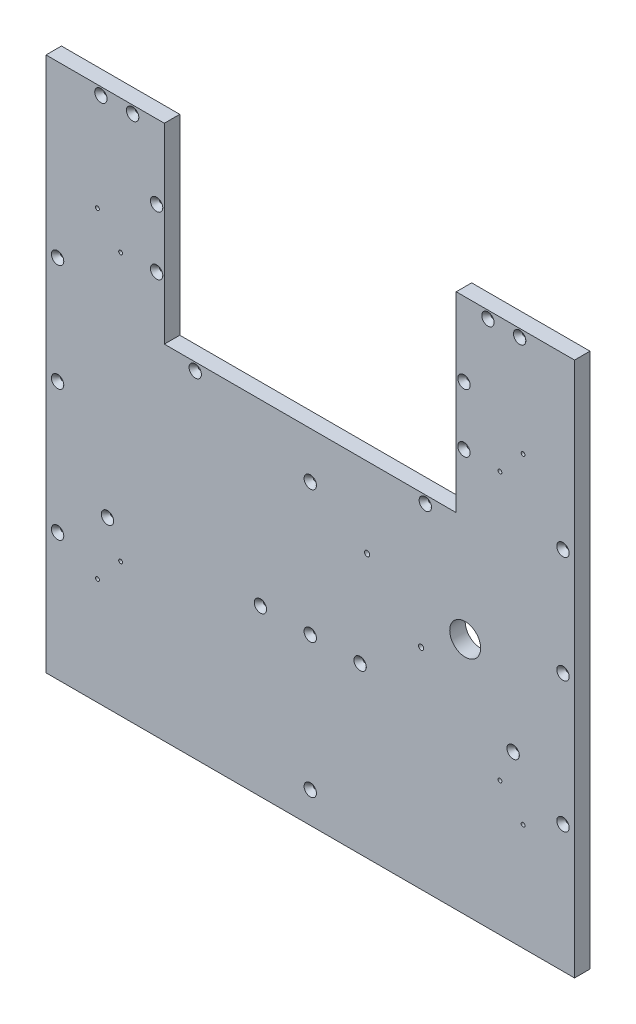
SolidWorks part; units mm, degrees
material "Beech"
ref_plane "Front Plane" through (0, 0, 0) normal (0, 0, 1) x (1, 0, 0)
ref_plane "Top Plane" through (0, 0, 0) normal (0, 1, 0) x (1, 0, 0)
ref_plane "Right Plane" through (0, 0, 0) normal (1, 0, 0) x (0, 0, -1)
sketch "Sketch1" plane through (0, 0, 0) normal (0, 0, 1) x (1, 0, 0)
  line L0 (341.3045, 12.7) -> (244.0045, 12.7)
  line L2 (341.3045, 12.7) -> (244.0045, 12.7) construction
  line L3 (244.0045, 12.7) -> (244.0045, -144.6)
  line L4 (244.0045, -144.6) -> (124.0045, -144.6)
  line L5 (341.3045, -455.5295) -> (-93.2955, -455.5295) construction
  line L6 (124.0045, -144.6) -> (124.0045, -427.3421)
  line L7 (124.0045, -427.3421) -> (341.3045, -427.3421)
  line L8 (341.3045, -427.3421) -> (341.3045, 12.7)
  line L12 (16.7045, -144.6) -> (231.3045, -144.6) construction
  point P18 (124.0045, -144.6)
  dimension "D1" = 28.1874
extrude "Boss-Extrude1" add sketch "Sketch1" along normal blind 12.7
mirror "Mirror1" about plane through (124.0045, -144.6, 12.7) normal (1, 0, 0) of "Boss-Extrude1"
hole_wizard "Hole1" positions "Sketch2" profile "Sketch3" legacy
sketch "Sketch2" plane through (124.0045, 10.4243, 12.7) normal (0, 0, 1) x (-1, 0, 0)
  line L12 (0, 0) -> (0, 155.0243) construction
  point P0 (-207.775, 333.0214)
  point P3 (-207.775, 225.489)
  point P6 (-207.775, 137.4243)
  point P9 (-172.1667, 4.0743)
  point P12 (-146.0833, 4.0743)
  point P15 (-94.6, 161.3743)
  point P21 (94.6, 161.3743)
  point P24 (146.0833, 4.0743)
  point P27 (172.1667, 4.0743)
  point P30 (207.775, 137.4243)
  point P33 (207.775, 225.489)
  point P36 (207.775, 333.0214)
  point P39 (166.7958, 301.9704)
  point P42 (40.9792, 301.9704)
  point P45 (-40.9792, 301.9704)
  point P48 (-166.7958, 301.9704)
  point P51 (0, 193.1243)
  point P54 (0, 301.9704)
  point P57 (0, 412.3664)
  point P80 (-126.35, 106.8243)
  point P82 (-126.35, 58.6243)
  point P96 (126.35, 58.6243)
  point P97 (126.35, 106.8243)
sketch "Sketch3" plane through (331.7795, -322.5971, 12.7) normal (1, 0, 0) x (0, -1, 0)
  line L0 (0, 0) -> (0, 32.7039)
  line L1 (0, 32.7039) -> (1.5875, 31.75)
  line L2 (1.5875, 31.75) -> (1.5875, 4.0177)
  line L3 (1.5875, 4.0177) -> (5.08, 0)
  line L4 (5.08, 0) -> (0, 0)
  line L5 (0, -14.3089) -> (0, 102.4216) construction
  line L6 (0, 32.7039) -> (-1.5875, 31.75) construction
  line L7 (-1.5875, 4.0177) -> (-5.08, 0) construction
  dimension "Diameter" = 3.175
  dimension "Depth" = 31.75
  dimension "C-Sink Diameter" = 10.16
  dimension "C-Sink Angle" = 82
  dimension "Drill Angle" = 118
hole_wizard "Hole2" positions "Sketch4" profile "Sketch5" legacy
sketch "Sketch4" plane through (124.0045, 10.4243, 0) normal (0, 0, -1) x (1, 0, 0)
  line L8 (155.95, -2.2757) -> (155.95, 437.7664) construction
  line L11 (175, -2.2757) -> (175, 437.7664) construction
  line L15 (155.95, -2.2757) -> (155.95, 107.7348)
  line L16 (155.95, 107.7348) -> (155.95, 217.7454)
  line L17 (155.95, 217.7454) -> (155.95, 327.7559)
  line L18 (155.95, 327.7559) -> (155.95, 437.7664)
  line L20 (175, -2.2757) -> (175, 85.7327)
  line L21 (175, 85.7327) -> (175, 173.7411)
  line L22 (175, 173.7411) -> (175, 261.7496)
  line L23 (175, 261.7496) -> (175, 349.758)
  line L24 (175, 349.758) -> (175, 437.7664)
  line L25 (0, 155.0243) -> (0, 437.7664) construction
  point P36 (155.95, 107.7348)
  point P40 (155.95, 327.7559)
  point P46 (175, 85.7327)
  point P52 (175, 349.758)
  point P77 (-175, 349.758)
  point P80 (-175, 85.7327)
  point P81 (-155.95, 327.7559)
  point P83 (-155.95, 107.7348)
sketch "Sketch5" plane through (-31.9455, -97.3105, 0) normal (1, 0, 0) x (0, 1, 0)
  line L0 (0, 0) -> (0, 32.7039)
  line L1 (0, 32.7039) -> (1.5875, 31.75)
  line L2 (1.5875, 31.75) -> (1.5875, 4.0177)
  line L3 (1.5875, 4.0177) -> (5.08, 0)
  line L4 (5.08, 0) -> (0, 0)
  line L5 (0, -14.3089) -> (0, 102.4216) construction
  line L6 (0, 32.7039) -> (-1.5875, 31.75) construction
  line L7 (-1.5875, 4.0177) -> (-5.08, 0) construction
  dimension "Diameter" = 3.175
  dimension "Depth" = 31.75
  dimension "C-Sink Diameter" = 10.16
  dimension "C-Sink Angle" = 82
  dimension "Drill Angle" = 118
hole_wizard "1 (1) Diameter Hole1" positions "Sketch6" profile "Sketch7" hole size "1" standard "ANSI Inch" end condition up to next
sketch "Sketch6" plane through (0, 0, 0) normal (0, 0, -1) x (-1, 0, 0)
  line L0 (-270.4295, -231.122) -> (-251.3795, -231.122) construction
  point P0 (-251.3795, -231.122)
  dimension "D1" = 19.05
sketch "Sketch7" plane through (251.3795, -231.122, 0) normal (1, 0, 0) x (0, 1, 0)
  line L0 (0, 0) -> (0, 12.7)
  line L1 (0, 12.7) -> (12.7, 12.7)
  line L2 (12.7, 12.7) -> (12.7, 0)
  line L5 (12.7, 0) -> (0, 0)
  line L11 (0, -6.35) -> (0, 107.95) construction
  dimension "Thru Hole Dia." = 25.4
  dimension "Thru Hole Depth" = 12.7
hole_wizard "#6 Clearance Hole1" positions "Sketch8" profile "Sketch9" hole size "#6" standard "ANSI Inch" end condition up to next
sketch "Sketch8" plane through (0, 0, 0) normal (0, 0, -1) x (-1, 0, 0)
  point P0 (-215.1525, -254.8561)
  point P2 (-170.7025, -210.4061)
sketch "Sketch9" plane through (215.1525, -254.8561, 0) normal (1, 0, 0) x (0, 1, 0)
  line L0 (0, 0) -> (0, 12.7)
  line L1 (0, 12.7) -> (2.1526, 12.7)
  line L2 (2.1526, 12.7) -> (2.1526, 0)
  line L5 (2.1526, 0) -> (0, 0)
  line L11 (0, -6.35) -> (0, 107.95) construction
  dimension "Thru Hole Dia." = 4.3053
  dimension "Thru Hole Depth" = 12.7
